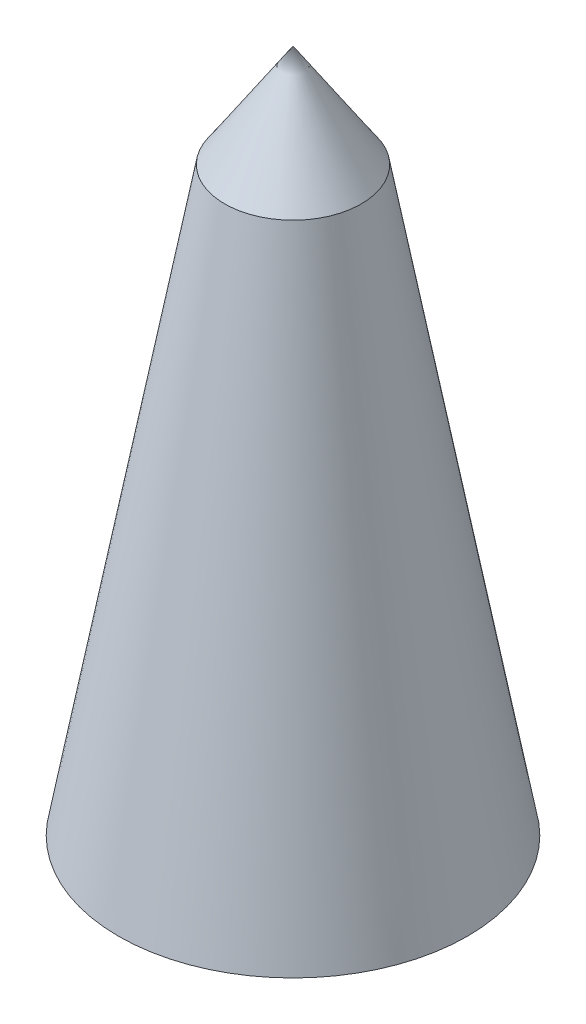
SolidWorks part; units mm, degrees
ref_plane "Front Plane" through (0, 0, 0) normal (0, 0, 1) x (1, 0, 0)
ref_plane "Top Plane" through (0, 0, 0) normal (0, 1, 0) x (1, 0, 0)
ref_plane "Right Plane" through (0, 0, 0) normal (1, 0, 0) x (0, 0, -1)
sketch "Sketch1" plane through (0, 0, 0) normal (0, 0, 1) x (1, 0, 0)
  line L0 (0, 200) -> (-20, 170)
  line L1 (-20, 170) -> (-51.054, 0)
  line L2 (-51.054, 0) -> (0, 0)
  line L3 (0, 0) -> (0, 200)
  dimension "D1" = 51.054
  dimension "D2" = 200
  dimension "D3" = 170
  dimension "D4" = 20
revolve "Revolve1" add sketch "Sketch1" angle 360 about L3
shell "Shell1" thickness 10 removed face at (0, 0, -51.054)
sketch "Sketch3" plane through (0, 0, 0) normal (0, -1, 0) x (1, 0, 0)
  circle A0 centre (0, 0) radius 44
  dimension "D1" = 88
extrude "Cut-Extrude1" cut sketch "Sketch3" against normal blind 10
thread "Thread1" pitch 2.1167 method cut profile "Thread Profile1" start angle 0, offset 2, length 12, pitch 2.1167, diameter 88
ref_plane "Plane1" through (44, -2, 0) normal (0, 0, 1) x (1, 0, 0)
sketch "Thread Profile1" plane through (44, -2, 0) normal (0, 0, 1) x (1, 0, 0)
  line L0 (0, 0) -> (0, 2.1167) construction
  line L1 (0, 0) -> (1.1457, 0.6615)
  line L2 (1.1457, 0.6615) -> (1.1457, 0.926)
  line L3 (1.1457, 0.926) -> (0, 1.5875)
  line L4 (1.1457, 0.7937) -> (0, 0.7937) construction
  line L11 (0, 0) -> (0, 1.5875)
  point P2 (0, 0)
  dimension "Pitch" = 2.1167
  dimension "Profile_Angle" = 60
  dimension "Profile_Land" = 0.2646
  dimension "Profile_Height" = 1.1457
sketch "Sketch9" plane through (0, 0, 0) normal (0, 0, 1) x (1, 0, 0)
  line L0 (0, 85) -> (0, 0) construction
  circle A0 centre (0, 85) radius 7.5
  dimension "D1" = 15
  dimension "D2" = 85
extrude "Boss-Extrude1" add sketch "Sketch9" along normal up to next and the other way up to next
fillet "Fillet1" radius 3 2 edges at (3.7654, 91.4863, -23.8817) (5.9021, 89.6276, 23.7951)
